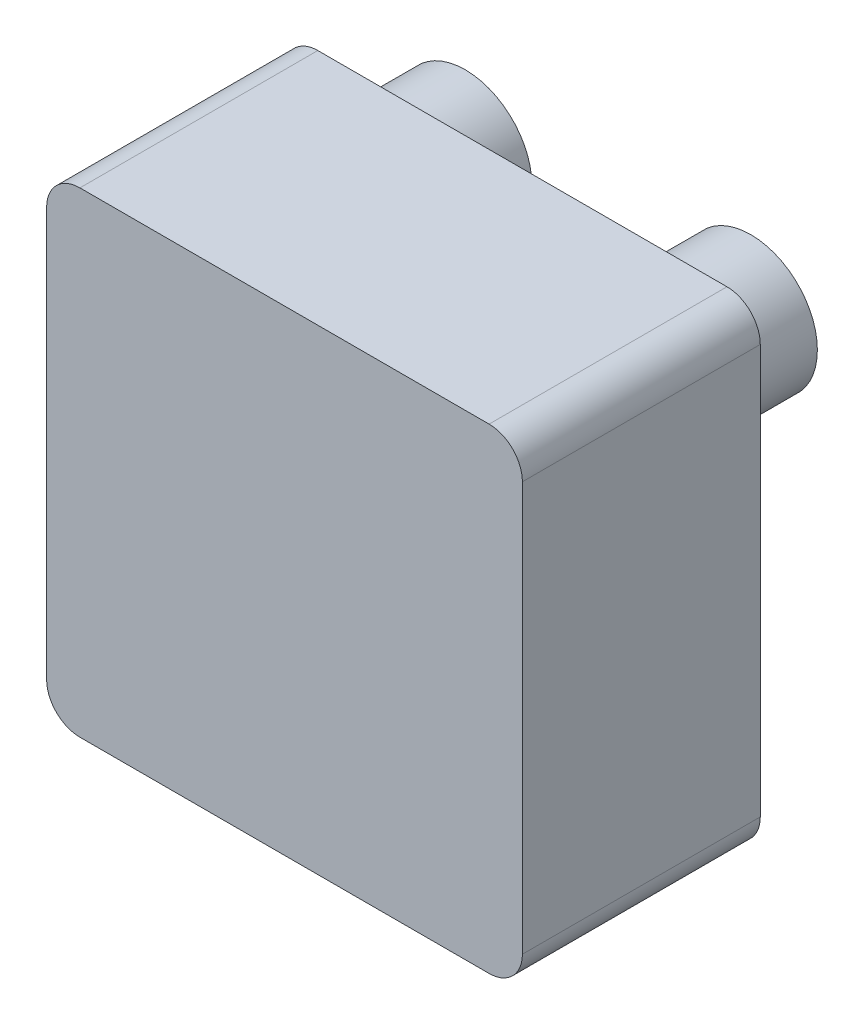
SolidWorks part; units mm, degrees
ref_plane "Front Plane" through (0, 0, 0) normal (0, 0, 1) x (1, 0, 0)
ref_plane "Top Plane" through (0, 0, 0) normal (0, 1, 0) x (1, 0, 0)
ref_plane "Right Plane" through (0, 0, 0) normal (1, 0, 0) x (0, 0, -1)
sketch "Sketch2" plane through (0, 0, 0) normal (0, 1, 0) x (1, 0, 0)
  line L1 (0, 0) -> (10, 0)
  line L2 (0, 0) -> (0, 5)
  line L3 (0, 5) -> (10, 5)
  line L4 (10, 0) -> (10, 5)
  dimension "D1" = 10
  dimension "D2" = 5
extrude "Boss-Extrude2" add sketch "Sketch2" along normal blind 10
sketch "Sketch3" plane through (0, 0, -5) normal (0, 0, -1) x (-1, 0, 0)
  line L0 (-10, 10) -> (0, 10) construction
  line L1 (-10, 10) -> (-10, 0) construction
  line L2 (0, 10) -> (0, 0) construction
  circle A0 centre (-8, 8) radius 1.4
  circle A1 centre (-2, 8) radius 1.4
  dimension "D1" = 2.8
  dimension "D2" = 2.8
  dimension "D4" = 2
  dimension "D3" = 2
  dimension "D5" = 2
  dimension "D6" = 2
extrude "Boss-Extrude3" add sketch "Sketch3" along normal blind 1.8
sketch "Sketch4" plane through (0, 0, 0) normal (0, -1, 0) x (1, 0, 0)
  line L0 (0.6, -5) -> (3.4, -5) construction
  line L1 (2, -5) -> (4.35, -5)
  line L2 (2, -5) -> (2, -4.65)
  line L3 (2, -4.65) -> (4.35, -4.65)
  line L4 (4.35, -5) -> (4.35, -4.65)
  line L5 (10, -5) -> (0, -5) construction
  line L6 (5.65, -5) -> (8, -5)
  line L7 (5.65, -5) -> (5.65, -4.65)
  line L8 (5.65, -4.65) -> (8, -4.65)
  line L9 (8, -5) -> (8, -4.65)
  line L10 (0, -5) -> (0, 0) construction
  line L11 (10, 0) -> (10, -5) construction
  dimension "D1" = 2
  dimension "D2" = 2
  dimension "D3" = 0.35
  dimension "D4" = 0.35
  dimension "D5" = 1.3
  dimension "D6" = 2.35
extrude "Cut-Extrude1" cut sketch "Sketch4" against normal blind 5
sketch "Sketch5" plane through (0, 0, 0) normal (0, -1, 0) x (1, 0, 0)
  line L0 (0, -2.5) -> (10, -2.5) construction
  line L1 (0, -5) -> (0, 0) construction
  line L2 (10, 0) -> (10, -5) construction
  line L3 (5, 0) -> (5, -5) construction
  line L4 (0, 0) -> (10, 0) construction
  line L5 (5.65, -5) -> (4.35, -5) construction
  circle A0 centre (5, -2.5) radius 1.2
  dimension "D1" = 2.4
extrude "Cut-Extrude2" cut sketch "Sketch5" against normal blind 3.5
fillet "Fillet1" radius 0.7 4 edges at (10, 0, -2.5) (0, 0, -2.5) (0, 10, -2.5) (10, 10, -2.5)
